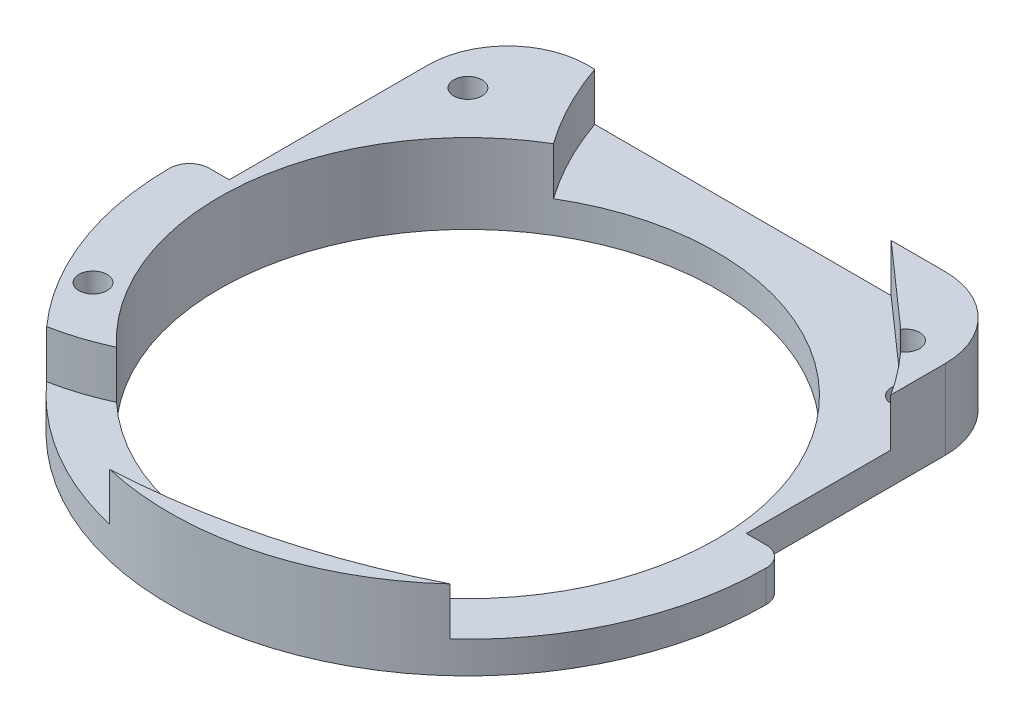
SolidWorks part; units mm, degrees
material "ABS"
ref_plane "Front Plane" through (0, 0, 0) normal (0, 0, 1) x (1, 0, 0)
ref_plane "Top Plane" through (0, 0, 0) normal (0, 1, 0) x (1, 0, 0)
ref_plane "Right Plane" through (0, 0, 0) normal (1, 0, 0) x (0, 0, -1)
sketch "Sketch1" plane through (0, 0, 0) normal (0, 1, 0) x (1, 0, 0)
  line L0 (-47.625, 0) -> (-47.625, 3.175)
  line L1 (47.625, -47.625) -> (-47.625, -47.625) construction
  line L2 (47.625, -47.625) -> (47.625, 47.625) construction
  line L3 (47.625, 47.625) -> (-47.625, 47.625) construction
  line L4 (-47.625, -47.625) -> (-47.625, 47.625) construction
  line L5 (47.625, -47.625) -> (-47.625, 47.625) construction
  line L6 (47.625, 47.625) -> (-47.625, -47.625) construction
  line L7 (-47.625, 3.175) -> (-41.275, 3.175)
  line L8 (-41.275, 3.175) -> (-41.275, 47.625)
  line L9 (-41.275, 47.625) -> (41.275, 47.625)
  line L10 (41.275, 47.625) -> (41.275, 3.175)
  line L11 (41.275, 3.175) -> (47.625, 3.175)
  line L12 (47.625, 3.175) -> (47.625, 0)
  arc A0 (-47.625, 0) -> (47.625, 0) centre (0, 0) ccw
  circle A1 centre (0, 0) radius 39.6875
  point P0 (0, 0)
  dimension "D4" = 79.375
  dimension "D1" = 95.25
  dimension "D2" = 3.175
  dimension "D3" = 6.35
extrude "Boss-Extrude1" add sketch "Sketch1" along normal blind 12.7
fillet "Fillet1" radius 12.7 2 edges at (41.275, 6.35, -47.625) (-41.275, 6.35, -47.625)
fillet "Fillet2" radius 3.175 2 edges at (47.625, 6.35, -3.175) (-47.625, 6.35, -3.175)
sketch "Sketch2" plane through (0, 12.7, 0) normal (0, 1, 0) x (1, 0, 0)
  line L1 (34.925, -34.925) -> (-34.925, -34.925) construction
  line L2 (34.925, -34.925) -> (34.925, 34.925) construction
  line L3 (34.925, 34.925) -> (-34.925, 34.925) construction
  line L4 (-34.925, -34.925) -> (-34.925, 34.925) construction
  line L5 (34.925, -34.925) -> (-34.925, 34.925) construction
  line L6 (34.925, 34.925) -> (-34.925, -34.925) construction
  circle A0 centre (-34.925, 34.925) radius 2.25
  circle A1 centre (34.925, 34.925) radius 2.25
  point P0 (0, 0)
  dimension "D1" = 4.5
  dimension "D2" = 69.85
extrude "Cut-Extrude1" cut sketch "Sketch2" against normal through all
sketch "Sketch8" plane through (0, 12.7, 0) normal (0, 1, 0) x (1, 0, 0)
  line L0 (-41.275, 34.925) -> (-41.275, 3.175) construction
  line L1 (28.575, 47.625) -> (-28.575, 47.625) construction
  line L2 (-15.875, 60.325) -> (0, 0) construction
  line L3 (-15.875, 60.325) -> (19.685, 60.325)
  line L4 (-8.5955, 68.5717) -> (30.2564, 34.2763)
  line L5 (0, 0) -> (10.5042, -39.916) construction
  arc A0 (29.6457, -25.9062) -> (4.9037, 39.0634) centre (0, 0) ccw
  arc A1 (-23.3666, 52.2704) -> (-8.5955, 68.5717) centre (-15.875, 60.325) cw
  arc A2 (-23.3666, 52.2704) -> (4.9037, 39.0634) centre (11.231, 89.4678) ccw
  arc A4 (29.6457, -25.9062) -> (34.4272, -30.0846) centre (32.0365, -27.9954) ccw
  arc A5 (34.4272, -30.0846) -> (30.2564, 34.2763) centre (0, 0) ccw
  circle A6 centre (-15.875, 60.325) radius 103.6539 construction
  point P0 (-15.875, 60.325)
  dimension "D3" = 11
  dimension "D4" = 39.37
  dimension "D5" = 6.35
  dimension "D7" = 50.8
  dimension "D8" = 41.275
  dimension "D1" = 25.4
  dimension "D2" = 12.7
  dimension "D6" = 35.56
sketch "Sketch6" plane through (0, 12.7, 0) normal (0, 1, 0) x (1, 0, 0)
  line L0 (-3.162, 0.2875) -> (3.162, -0.2875) construction
  line L1 (-42.3702, 3.8527) -> (-15.875, 60.325) construction
  line L2 (-5.0012, 61.9863) -> (2.8254, 10.7575) construction
  line L3 (-49.1877, -31.6945) -> (-48.8846, -41.276)
  line L4 (32.3576, 36.6566) -> (-25.4911, 87.7208)
  line L5 (-8.5955, 68.5717) -> (30.2564, 34.2763) construction
  circle A0 centre (-15.875, 60.325) radius 103.6539 construction
  arc A1 (29.6457, -25.9062) -> (34.4272, -30.0846) centre (32.0365, -27.9954) ccw construction
  circle A2 centre (-23.5527, 40.8561) radius 28.4126 construction
  arc A3 (-36.2298, -35.0355) -> (-13.5613, 30.6863) centre (-42.3702, 3.8527) ccw construction
  arc A4 (-26.7884, 58.9472) -> (-5.0012, 61.9863) centre (-15.875, 60.325) cw construction
  arc A5 (-26.7884, 58.9472) -> (-13.5613, 30.6863) centre (23.6115, 65.3103) ccw construction
  arc A6 (-36.2298, -35.0355) -> (-35.2394, -41.3078) centre (-35.7346, -38.1717) ccw construction
  arc A7 (-35.2394, -41.3078) -> (2.8254, 10.7575) centre (-42.3702, 3.8527) ccw construction
  arc A8 (-49.1877, -31.6945) -> (-15.8846, 28.5223) centre (-42.3702, 3.8527) ccw
  arc A9 (-48.8846, -41.276) -> (36.0435, -33.0392) centre (-15.875, 60.325) ccw
  arc A10 (36.0435, -33.0392) -> (32.3576, 36.6566) centre (0, 0) ccw
  arc A11 (34.4272, -30.0846) -> (30.2564, 34.2763) centre (0, 0) ccw construction
  arc A13 (-15.8846, 28.5223) -> (-25.4911, 87.7208) centre (23.6115, 65.3103) cw
  point P10 (-15.875, 60.325)
  dimension "D2" = 39.37
  dimension "D3" = 6.35
  dimension "D6" = 50.8
  dimension "D7" = 3.175
  dimension "D8" = 3.175
  dimension "D9" = 3.175
  dimension "D1" = 62.3789
  dimension "D4" = 51.8232
  dimension "D5" = 71.5881
extrude "Cut-Extrude2" cut sketch "Sketch6" against normal blind 7.62
sketch "Sketch9" plane through (0, 12.7, 0) normal (0, 1, 0) x (1, 0, 0)
  line L0 (0, 0) -> (-41.2445, -23.8125) construction
  line L1 (19.9319, 47.625) -> (-27.3839, 47.625) construction
  arc A0 (-47.625, 0) -> (-35.548, -31.6936) centre (0, 0) ccw construction
  circle A1 centre (-37.9449, -21.9075) radius 2.25
  dimension "D3" = 4.5
  dimension "D1" = 30
  dimension "D2" = 3.81
extrude "Cut-Extrude3" cut sketch "Sketch9" against normal through all
